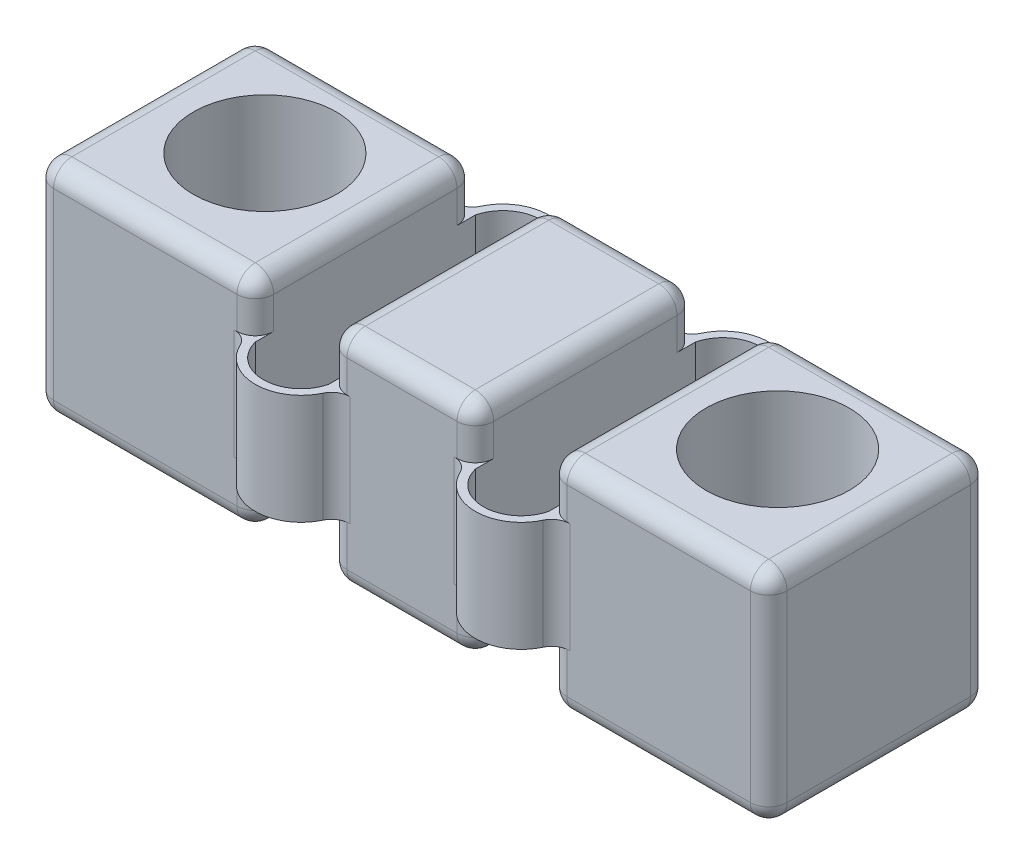
SolidWorks part; units mm, degrees
material "PC 高粘度"
ref_plane "前视基准面" through (0, 0, 0) normal (0, 0, 1) x (1, 0, 0)
ref_plane "上视基准面" through (0, 0, 0) normal (0, 1, 0) x (1, 0, 0)
ref_plane "右视基准面" through (0, 0, 0) normal (1, 0, 0) x (0, 0, -1)
sketch "草图1" plane through (0, 0, 0) normal (0, 0, 1) x (1, 0, 0)
  line L1 (-10.3378, 4.375) -> (9.6622, 4.375)
  line L2 (-10.3378, 4.375) -> (-10.3378, -1.625)
  line L3 (-10.3378, -1.625) -> (9.6622, -1.625)
  line L4 (9.6622, 4.375) -> (9.6622, -1.625)
  dimension "D1" = 20
  dimension "D2" = 6
extrude "凸台-拉伸3" add sketch "草图1" along normal blind 8
sketch "草图4" plane through (0, 0, 0) normal (0, 1, 0) x (1, 0, 0)
  line L0 (9.6622, -8) -> (3.6622, -8)
  line L1 (9.6622, -8) -> (-10.3378, -8) construction
  line L2 (3.6622, -8) -> (1.6622, -8)
  line L3 (3.6622, -8) -> (3.6622, 0)
  line L4 (9.6622, 0) -> (-10.3378, 0) construction
  line L5 (9.6622, -8) -> (9.6622, -7)
  line L6 (9.6622, -8) -> (9.6622, 0) construction
  line L7 (9.6622, -7) -> (3.6622, -7)
  line L8 (3.6622, -7) -> (1.6622, -7)
  line L9 (1.6622, -7) -> (1.6622, -8)
  line L10 (9.6622, 0) -> (9.6622, -1)
  line L11 (9.6622, -1) -> (3.6622, -1)
  line L12 (3.6622, -1) -> (1.6622, -1)
  line L13 (1.6622, -1) -> (1.6622, 0)
  line L14 (1.6622, 0) -> (3.6622, 0)
  line L15 (3.6622, -1) -> (3.6622, -0.5)
  line L16 (1.6622, -1) -> (1.6622, -0.5)
  line L17 (-4.3437, -1.0014) -> (-4.3378, -7)
  line L18 (1.6622, 0) -> (2.6622, 0)
  line L19 (-0.3378, -8) -> (-2.3378, -8)
  line L20 (-2.3378, -8) -> (-4.3378, -8)
  line L21 (-4.3378, -8) -> (-10.3378, -8)
  line L22 (-2.3378, -8) -> (-2.3378, 0)
  line L23 (-4.3378, -8) -> (-4.3378, -7.5)
  line L24 (-10.3378, 0) -> (-10.3378, -1)
  line L25 (-10.3378, -8) -> (-10.3378, 0) construction
  line L26 (-10.3378, -1) -> (-2.3378, -1)
  line L27 (-2.3378, -1) -> (-2.3378, -7)
  line L28 (-2.3378, -7) -> (-10.3378, -7)
  line L29 (-4.3378, -8) -> (-4.3378, 0)
  line L30 (-4.3378, -0.5) -> (-4.3378, 0)
  line L31 (-2.3378, -1) -> (-2.3378, -0.5)
  line L32 (-2.3378, -0.5) -> (-2.3378, 0)
  line L33 (-4.3378, 0) -> (-3.3378, 0)
  line L34 (-4.3378, -7.5) -> (-4.3378, -7)
  line L35 (-4.3378, -7) -> (-2.3378, -7)
  line L36 (-2.3378, -7.5) -> (-2.3378, -8)
  line L37 (-2.3378, -1) -> (-2.3378, -7)
  line L38 (-2.3378, -1) -> (-4.3378, -1)
  line L39 (1.6622, -7) -> (1.6622, -1)
  line L40 (3.6622, -1) -> (3.6622, -7)
  line L41 (-2.3378, -8) -> (-3.3378, -8)
  line L42 (1.6622, -8) -> (2.6622, -8)
  line L43 (2.6622, -8) -> (3.6622, -8)
  line L44 (3.6622, -7) -> (2.6622, -7)
  line L45 (2.6622, -7) -> (1.6622, -7)
  line L47 (-2.3378, -1) -> (1.6622, -1)
  line L48 (1.6622, -7) -> (1.6622, -1)
  line L49 (-2.3378, -7) -> (1.6622, -7)
  line L50 (-10.3378, 0) -> (-4.3378, 0)
  line L51 (-3.3378, 0) -> (-2.3378, 0)
  line L52 (1.6622, 0) -> (-2.3378, 0)
  line L53 (-4.5626, -1) -> (-4.3378, -1)
  line L54 (-4.3378, -1) -> (-4.3437, -1.0014)
  line L55 (3.6622, 0) -> (9.6622, 0)
  line L56 (-0.3378, -8) -> (1.6622, -8)
  line L57 (-4.3378, -8) -> (-4.3378, -7.5)
  line L58 (-10.3378, -8) -> (-10.3378, -7)
  circle A1 centre (2.6622, -1.25) radius 1.25
  circle A2 centre (-3.3378, -1.25) radius 1.25
  circle A3 centre (-3.3378, -1.25) radius 1.0308
  circle A4 centre (-3.3378, -6.75) radius 1.25
  circle A7 centre (2.6622, -6.75) radius 1.25
  circle A8 centre (-3.3378, -6.75) radius 1.0308
  circle A9 centre (2.6622, -6.75) radius 1.0308
  circle A10 centre (2.6622, -1.25) radius 1.0308
  dimension "D1" = 6
  dimension "D2" = 2
  dimension "D3" = 6
  dimension "D4" = 2
extrude "切除-拉伸4" cut sketch "草图4" against normal mid plane 10 contours A2 L29 L50 L24 L26 | A4 L28 L58 L21 L23 | A4 L23 L20 | A4 L20 L22 | A7 L49 A4 L22 L19 L56 L9 | A7 L9 L2 | A7 L2 L3 | A7 L3 L0 L5 L7 | A1 L11 L10 L55 L3 | A1 L3 L14 | A1 L14 L13 | A2 L47 A1 L13 L52 L22 | A2 L22 L51 | A2 L33 L29 | L26 A3 | L28 A8 | L8 A9 | L12 A10 | L29 A3 L22 L26 | A3 L29 A2 L37 | A4 L37 A2 L29 | A8 L37 A4 L29 | L22 A8 L29 L28 | A7 L40 A1 L48 | A9 L40 A7 L48 | L3 A9 L39 L8 | A10 L48 A1 L40 | L39 A10 L3 L12 region at (6.6953, 0, 7.5036) region at (3.4233, 0, 7.857) region at (1.9011, 0, 7.857) region at (-0.3378, 0, 7.5111) region at (2.6622, 0, 6.4412) region at (2.6622, 0, 7.3254) region at (2.6622, 0, 5.6969) region at (2.6622, 0, 4) region at (-2.5767, 0, 7.857) region at (2.6622, 0, 2.4776) region at (-4.0989, 0, 7.857) region at (-3.3378, 0, 6.4412) region at (-3.3378, 0, 7.3254) region at (2.6622, 0, 1.5588) region at (-7.3709, 0, 7.5036) region at (-3.3378, 0, 5.6969) region at (-3.3378, 0, 4) region at (-0.3378, 0, 0.4889) region at (2.6622, 0, 0.6746) region at (6.6953, 0, 0.4964) region at (-3.3378, 0, 2.4776) region at (1.9011, 0, 0.143) region at (3.4233, 0, 0.143) region at (-3.3378, 0, 1.5588) region at (-3.3378, 0, 0.6746) region at (-2.5767, 0, 0.143) region at (-4.0989, 0, 0.143) region at (-7.3709, 0, 0.4964)
ref_plane "基准面1" through (0, 3, 0) normal (0, 1, 0) x (1, 0, 0)
sketch "草图5" plane through (0, 3, 0) normal (0, 1, 0) x (1, 0, 0)
  line L0 (-4.5626, -7) -> (-4.3378, -7)
  line L1 (-4.5626, -1) -> (-4.3378, -1)
  line L2 (-2.1131, -1) -> (-2.3378, -1)
  line L3 (1.4374, -1) -> (1.6622, -1)
  line L4 (1.4374, -7) -> (1.6622, -7)
  line L7 (3.6622, -1) -> (3.8869, -1)
  line L8 (3.6622, -7) -> (3.8869, -7)
  line L9 (-2.3378, -7) -> (-2.1131, -7)
  arc A0 (-4.5626, -7) -> (-2.1131, -7) centre (-3.3378, -6.75) ccw
  arc A1 (-4.3378, -7) -> (-2.3378, -7) centre (-3.3378, -6.75) ccw
  arc A2 (-4.5626, -1) -> (-2.1131, -1) centre (-3.3378, -1.25) cw
  arc A3 (-4.3378, -1) -> (-2.3378, -1) centre (-3.3378, -1.25) cw
  arc A4 (-2.3378, -1) -> (-4.3378, -1) centre (-3.3378, -1.25) ccw construction
  arc A5 (3.8869, -1) -> (1.4374, -1) centre (2.6622, -1.25) ccw
  arc A6 (1.4374, -7) -> (3.8869, -7) centre (2.6622, -6.75) ccw
  arc A7 (3.6622, -1) -> (1.6622, -1) centre (2.6622, -1.25) ccw
  arc A8 (1.6622, -7) -> (3.6622, -7) centre (2.6622, -6.75) ccw
extrude "切除-拉伸6" cut sketch "草图5" along normal through all
ref_plane "基准面2" through (0, 0, 0) normal (0, 1, 0) x (1, 0, 0)
sketch "草图7" plane through (0, 0, 0) normal (0, 1, 0) x (1, 0, 0)
  line L0 (-4.5626, -7) -> (-4.3378, -7)
  line L1 (3.6622, -1) -> (3.8869, -1) construction
  line L2 (3.8869, -7) -> (3.6622, -7) construction
  line L3 (1.4374, -7) -> (1.6622, -7)
  line L4 (1.4374, -1) -> (1.6622, -1)
  line L5 (-4.5626, -1) -> (-4.3378, -1)
  line L6 (-2.3378, -1) -> (-2.1131, -1)
  line L7 (3.6622, -1) -> (3.8869, -1)
  line L8 (3.6622, -7) -> (3.8869, -7)
  line L9 (-2.3378, -7) -> (-2.1131, -7)
  arc A0 (-4.3378, -7) -> (-2.3378, -7) centre (-3.3378, -6.75) ccw
  arc A1 (-4.5626, -7) -> (-2.1131, -7) centre (-3.3378, -6.75) ccw
  arc A2 (-4.3378, -1) -> (-2.3378, -1) centre (-3.3378, -1.25) cw
  arc A3 (-4.5626, -1) -> (-2.1131, -1) centre (-3.3378, -1.25) cw
  arc A4 (1.6622, -1) -> (3.6622, -1) centre (2.6622, -1.25) cw
  arc A5 (1.4374, -1) -> (3.8869, -1) centre (2.6622, -1.25) cw
  arc A6 (3.8869, -1) -> (1.4374, -1) centre (2.6622, -1.25) ccw construction
  arc A7 (1.6622, -7) -> (3.6622, -7) centre (2.6622, -6.75) ccw
  arc A8 (1.4374, -7) -> (3.8869, -7) centre (2.6622, -6.75) ccw
  arc A9 (1.4374, -7) -> (3.8869, -7) centre (2.6622, -6.75) ccw construction
extrude "切除-拉伸7" cut sketch "草图7" against normal through all
hole_wizard "M3.5 间隙孔1" positions "草图10" profile "草图9" hole size "M3.5" standard "ISO" end condition through all
sketch "草图10" plane through (0, 4.375, 0) normal (0, 1, 0) x (1, 0, 0)
  point P0 (-7.2912, -3.7849)
  point P2 (6.6893, -3.7849)
sketch "草图9" plane through (-7.2912, 4.375, 3.7849) normal (1, 0, 0) x (0, 0, 1)
  line L0 (0, 0) -> (0, 6)
  line L1 (0, 6) -> (1.95, 6)
  line L2 (1.95, 6) -> (1.95, 0)
  line L5 (1.95, 0) -> (0, 0)
  line L11 (0, -6.35) -> (0, 107.95) construction
  dimension "通孔孔直径" = 3.9
  dimension "通孔孔深度" = 6
fillet "圆角4" radius 0.5 4 edges at (-10.3378, 1.375, 7) (-10.3378, 4.375, 4) (-10.3378, 1.375, 1) (-7.3378, 4.375, 1)
fillet "圆角5" radius 0.5 7 edges at (-7.0878, -1.625, 1) (-10.1914, -1.625, 1.1464) (-10.3378, -1.625, 4) (-10.1914, -1.625, 6.8536) (-10.1914, 4.2286, 6.8536) (-7.0878, -1.625, 7) (-7.0878, 4.375, 7)
fillet "圆角6" radius 0.5 1 edges at (-4.5626, 1.5, 7)
fillet "圆角7" radius 0.5 1 edges at (-2.1131, 1.5, 7)
fillet "圆角8" radius 0.5 1 edges at (1.4374, 1.5, 7)
fillet "圆角9" radius 0.5 1 edges at (3.8869, 1.5, 7)
fillet "圆角10" radius 0.5 1 edges at (-4.5626, 1.5, 1)
fillet "圆角11" radius 0.5 2 edges at (3.8869, 1.5, 1) (-2.1131, 1.5, 1)
fillet "圆角12" radius 0.5 1 edges at (1.4374, 1.5, 1)
fillet "圆角13" radius 0.5 10 edges at (-4.3378, 3.4375, 1) (-4.3378, 4.2286, 1.1464) (-4.3378, 3.4375, 7) (-4.3378, 4.2286, 6.8536) (-4.3378, -0.5625, 7) (-4.3378, -1.4786, 6.8536) (-4.3378, -0.5625, 1) (-4.3378, -1.4786, 1.1464) (-4.3378, 4.375, 4) (-4.3378, -1.625, 4)
fillet "圆角14" radius 0.5 7 edges at (9.6622, 1.375, 7) (9.6622, 1.375, 1) (9.6622, -1.625, 4) (9.6622, 4.375, 4) (6.6622, 4.375, 7) (6.6622, 4.375, 1) (3.6622, 4.375, 4)
fillet "圆角15" radius 0.5 7 edges at (3.8086, 4.2286, 1.1464) (9.5157, -1.4786, 6.8536) (9.5157, -1.4786, 1.1464) (3.6622, 3.4375, 1) (3.6622, -1.625, 4) (6.4122, -1.625, 7) (6.4122, -1.625, 1)
fillet "圆角16" radius 0.5 6 edges at (3.8086, -1.4786, 6.8536) (3.8086, -1.4786, 1.1464) (3.8086, 4.2286, 6.8536) (3.6622, -0.5625, 7) (3.6622, -0.5625, 1) (3.6622, 3.4375, 7)
fillet "圆角18" radius 0.5 5 edges at (1.6622, -0.8125, 1) (-2.3378, 3.6875, 1) (-2.3378, -0.8125, 1) (-2.3378, -0.8125, 7) (-2.3378, 3.6875, 7)
fillet "圆角19" radius 0.5 1 edges at (1.6622, -0.8125, 7)
fillet "圆角20" radius 0.5 16 edges at (-0.0878, 4.375, 7) (-2.1914, 4.375, 6.8536) (-2.3378, 4.375, 4) (-2.1914, 4.375, 1.1464) (1.5157, -1.625, 1.1464) (-0.3378, -1.625, 1) (-2.1914, -1.625, 1.1464) (-2.3378, -1.625, 4) (-2.1914, -1.625, 6.8536) (-0.3378, -1.625, 7) (1.5157, -1.625, 6.8536) (1.6622, -1.625, 4) (1.6622, 3.6875, 1) (1.6622, 4.375, 4) (-0.0878, 4.375, 1) (1.6622, 3.6875, 7)
